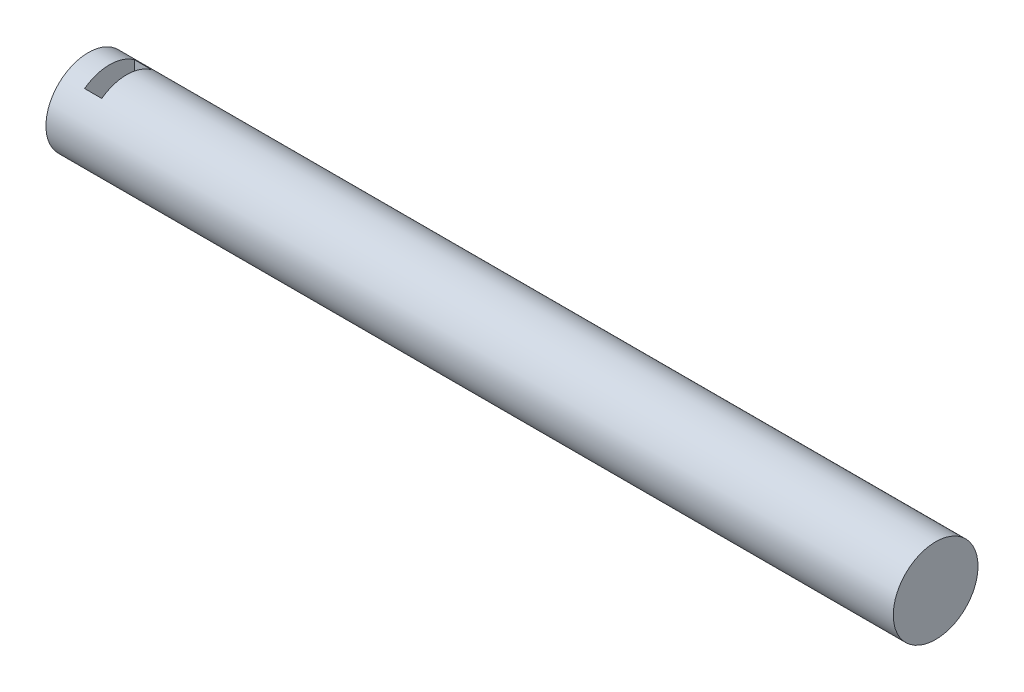
SolidWorks part; units mm, degrees
ref_plane "Front Plane" through (0, 0, 0) normal (0, 0, 1) x (1, 0, 0)
ref_plane "Top Plane" through (0, 0, 0) normal (0, 1, 0) x (1, 0, 0)
ref_plane "Right Plane" through (0, 0, 0) normal (1, 0, 0) x (0, 0, -1)
sketch "Sketch2" plane through (0, 0, 0) normal (1, 0, 0) x (0, 0, -1)
  circle A0 centre (0, 0) radius 20
extrude "Boss-Extrude1" add sketch "Sketch2" along normal blind 400
ref_plane "Plane1" through (0, 20, 0) normal (0, 1, 0) x (1, 0, 0)
sketch "Sketch3" plane through (0, 20, 0) normal (0, 1, 0) x (1, 0, 0)
  line L0 (0, -20) -> (0, 20)
  line L1 (0, -20) -> (0, 20) construction
  line L2 (0, 20) -> (400, 20)
  line L4 (400, 20) -> (400, -20)
  line L6 (400, -20) -> (0, -20)
  line L8 (10, 11.7541) -> (10, -11.7719)
  line L9 (10, -11.7719) -> (18.1241, -11.7719)
  line L10 (18.1241, -11.7719) -> (18.1241, 11.7541)
  line L11 (18.1241, 11.7541) -> (10, 11.7541)
  dimension "D1" = 10
extrude "Cut-Extrude1" cut sketch "Sketch3" against normal blind 24
sketch "Sketch5" plane through (18.1241, 0, 0) normal (-1, 0, 0) x (0, 0, 1)
  line L0 (-11.5553, -4.0364) -> (10.2362, -4.0364)
  line L1 (10.2362, -4.0364) -> (10.2362, 3.3505)
  line L2 (10.2362, 3.3505) -> (-11.5553, 3.3505)
  line L3 (-11.5553, 3.3505) -> (-11.5553, -4.0364)
extrude "Cut-Extrude2" cut sketch "Sketch5" against normal blind 17
extrude "Cut-Extrude3" cut sketch "Sketch5<2>" along normal blind 11
sketch "Sketch5<2>" plane through (18.1241, 0, 0) normal (-1, 0, 0) x (0, 0, 1) same geometry as "Sketch5"
equation "\"shaft\"= 4cm"
equation "\"length\"= 20cm"
equation "\"D1@Sketch2\"=\"shaft\""
equation "\"D1@Boss-Extrude1\"=\"length\"*2"
